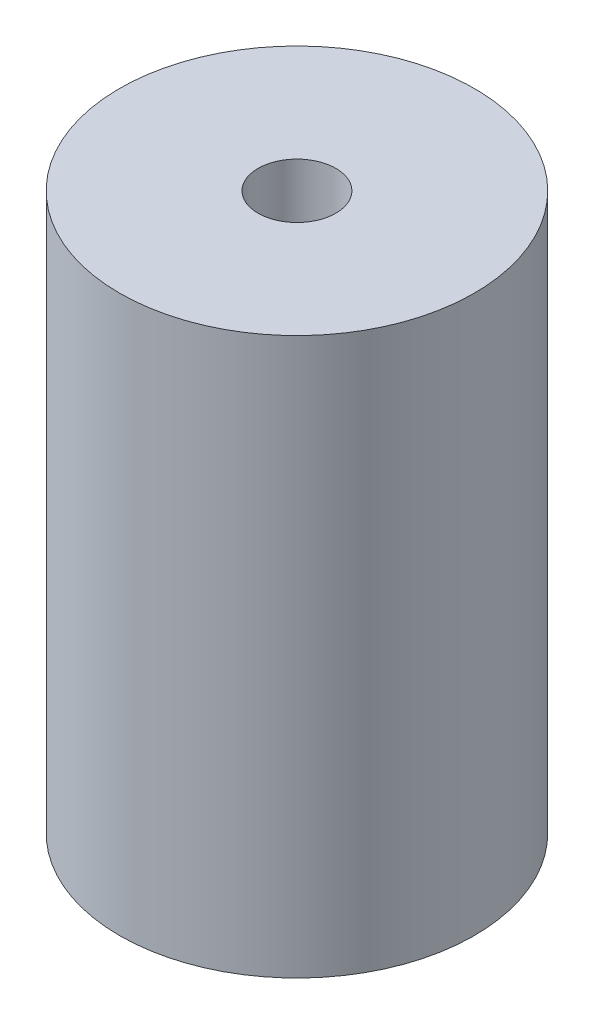
SolidWorks part; units mm, degrees
ref_plane "Front Plane" through (0, 0, 0) normal (0, 0, 1) x (1, 0, 0)
ref_plane "Top Plane" through (0, 0, 0) normal (0, 1, 0) x (1, 0, 0)
ref_plane "Right Plane" through (0, 0, 0) normal (1, 0, 0) x (0, 0, -1)
sketch "Sketch1" plane through (0, 0, 0) normal (0, 1, 0) x (1, 0, 0)
  circle A0 centre (0, 0) radius 1.3982
  circle A1 centre (0, 0) radius 6.375
  circle A2 centre (0, 0) radius 6.375
  point P25 (0, 0)
  dimension "D1" = 12.75
extrude "Boss-Extrude1" add sketch "Sketch1" along normal blind 17 and the other way blind 3 contours A1 A0 region at (-6.1947, 0, 0)
extrude "Boss-Extrude2" add sketch "Sketch1<3>" against normal blind 3 separate body contours A2 A1 region at (-6.1947, 0, 0)
sketch "Sketch1<3>" plane through (0, 0, 0) normal (0, 1, 0) x (1, 0, 0) same geometry as "Sketch1"
sketch "Sketch2" plane through (0, 0, 0) normal (1, 0, 0) x (0, 0, -1)
  line L0 (0, 0) -> (0, 2)
  line L1 (0, 4) -> (0, 6)
  circle A0 centre (0, 3) radius 1
  dimension "D1" = 2
sketch "Sketch3" plane through (0, -3, 0) normal (0, -1, 0) x (1, 0, 0)
  circle A0 centre (0, 9.6613) radius 0.75
  circle A2 centre (9.1884, 2.9855) radius 0.75
  circle A3 centre (5.6787, -7.8161) radius 0.75
  circle A4 centre (-5.6787, -7.8161) radius 0.75
  circle A5 centre (-9.1884, 2.9855) radius 0.75
  point P14 (0, 0)
  dimension "D1" = 5
sketch "Sketch4" plane through (0, -3, 0) normal (0, -1, 0) x (1, 0, 0)
  circle A0 centre (0, 0) radius 3.5
